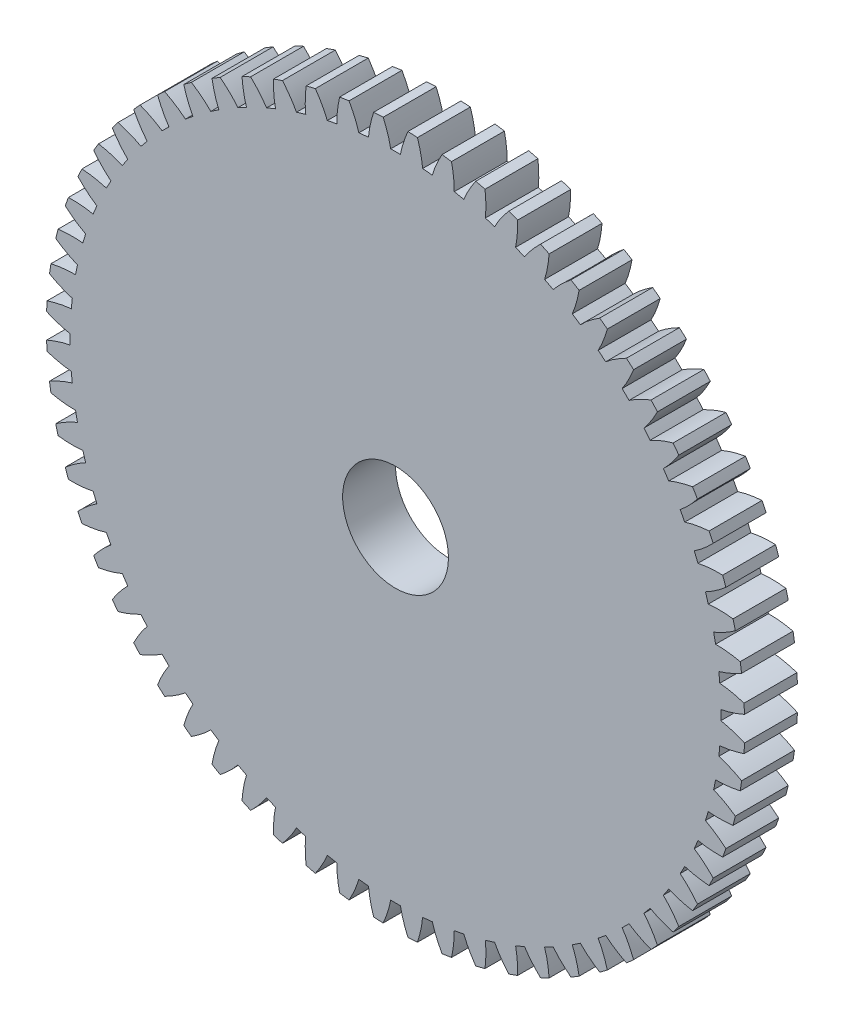
SolidWorks part; units mm, degrees
ref_plane "前视基准面" through (0, 0, 0) normal (0, 0, 1) x (1, 0, 0)
ref_plane "上视基准面" through (0, 0, 0) normal (0, 1, 0) x (1, 0, 0)
ref_plane "右视基准面" through (0, 0, 0) normal (1, 0, 0) x (0, 0, -1)
other "Configuration Table"
sketch "草图1" plane through (0, 0, 0) normal (0, 0, 1) x (1, 0, 0)
  line L0 (0, 0) -> (6.4, 0) construction
  line L1 (0, 0) -> (6.3981, 0.1571) construction
  line L2 (0, 0) -> (6.0135, 0.0774)
  line L3 (6.3981, 0.1571) -> (6.3981, -0.1571) construction
  line L4 (0, 0) -> (6.0135, -0.0774)
  circle A0 centre (0, 0) radius 6.6
  circle A1 centre (0, 0) radius 6.4 construction
  circle A2 centre (0, 0) radius 6.15
  circle A3 centre (0, 0) radius 6.014 construction
  circle A4 centre (0, 0) radius 1
  spline S0 degree 4 poles (6.0135, 0.0774) (6.0364, 0.0777) (6.0821, 0.0805) (6.2092, 0.0994) (6.4457, 0.1641) (6.7919, 0.3115) (7.2318, 0.5835) (7.7411, 1.0106) (8.2566, 1.5947) (8.7248, 2.311) (9.1179, 3.145) (9.4047, 4.0207) (9.5908, 4.9228) (9.686, 5.8846) (9.6791, 7.0814) (9.4879, 8.498) (9.0278, 10.0946) (8.2487, 11.7677) (7.2377, 13.3106) (6.0282, 14.7025) (4.6513, 15.9284) (3.1363, 16.9779) (1.7135, 17.7363) (0.5462, 18.2255) (-0.3224, 18.5269) (-0.982, 18.7296) (-1.647, 18.9089) (-2.322, 19.0593) (-2.9983, 19.1806) (-3.571, 19.2628) (-4.02, 19.3168) (-4.4511, 19.3563) (-4.803, 19.3824) (-5.2049, 19.403) (-5.4653, 19.4122) (-5.886, 19.421) (-6.2134, 19.4187) (-6.6109, 19.4119) (-6.965, 19.3963) (-7.3463, 19.3746) (-7.7078, 19.3453) (-7.9912, 19.3185) (-8.1717, 19.298) (-8.2653, 19.2873) knots 0 0 0 0 0 0.002802 0.005604 0.015718 0.02996 0.048734 0.068727 0.096889 0.125051 0.153212 0.181374 0.209535 0.237696 0.271429 0.327752 0.384075 0.440398 0.496721 0.553044 0.609367 0.66569 0.722013 0.750174 0.764255 0.778336 0.806497 0.834659 0.84874 0.86282 0.876901 0.890982 0.900036 0.909091 0.920455 0.931818 0.943182 0.954545 0.965909 0.977273 0.988636 1 1 1 1 1 construction
  spline S1 degree 4 poles (6.0135, 0.0774) (6.0364, 0.0777) (6.0821, 0.0805) (6.2092, 0.0994) (6.4457, 0.1641) (6.7919, 0.3115) (7.2318, 0.5835) (7.7411, 1.0106) (8.2566, 1.5947) (8.7248, 2.311) (9.1179, 3.145) (9.4047, 4.0207) (9.5908, 4.9228) (9.686, 5.8846) (9.6791, 7.0814) (9.4879, 8.498) (9.0278, 10.0946) (8.2487, 11.7677) (7.2377, 13.3106) (6.0282, 14.7025) (4.6513, 15.9284) (3.1363, 16.9779) (1.7135, 17.7363) (0.5462, 18.2255) (-0.3224, 18.5269) (-0.982, 18.7296) (-1.647, 18.9089) (-2.322, 19.0593) (-2.9983, 19.1806) (-3.571, 19.2628) (-4.02, 19.3168) (-4.4511, 19.3563) (-4.803, 19.3824) (-5.1, 19.3976) (-5.2354, 19.4034) (-5.3025, 19.4059) knots 0 0 0 0 0 0.002802 0.005604 0.015718 0.02996 0.048734 0.068727 0.096889 0.125051 0.153212 0.181374 0.209535 0.237696 0.271429 0.327752 0.384075 0.440398 0.496721 0.553044 0.609367 0.66569 0.722013 0.750174 0.764255 0.778336 0.806497 0.834659 0.84874 0.86282 0.876901 0.890982 0.900036 0.909091 0.909091 0.909091 0.909091 0.909091
  spline S2 degree 4 poles (6.0135, -0.0774) (6.0364, -0.0777) (6.0821, -0.0805) (6.2092, -0.0994) (6.4457, -0.1641) (6.7919, -0.3115) (7.2318, -0.5835) (7.7411, -1.0106) (8.2566, -1.5947) (8.7248, -2.311) (9.1179, -3.145) (9.4047, -4.0207) (9.5908, -4.9228) (9.686, -5.8846) (9.6791, -7.0814) (9.4879, -8.498) (9.0278, -10.0946) (8.2487, -11.7677) (7.2377, -13.3106) (6.0282, -14.7025) (4.6513, -15.9284) (3.1363, -16.9779) (1.7135, -17.7363) (0.5462, -18.2255) (-0.3224, -18.5269) (-0.982, -18.7296) (-1.647, -18.9089) (-2.322, -19.0593) (-2.9983, -19.1806) (-3.571, -19.2628) (-4.02, -19.3168) (-4.4511, -19.3563) (-4.803, -19.3824) (-5.2049, -19.403) (-5.4653, -19.4122) (-5.886, -19.421) (-6.2134, -19.4187) (-6.6109, -19.4119) (-6.965, -19.3963) (-7.3463, -19.3746) (-7.7078, -19.3453) (-7.9912, -19.3185) (-8.1717, -19.298) (-8.2653, -19.2873) knots 0 0 0 0 0 0.002802 0.005604 0.015718 0.02996 0.048734 0.068727 0.096889 0.125051 0.153212 0.181374 0.209535 0.237696 0.271429 0.327752 0.384075 0.440398 0.496721 0.553044 0.609367 0.66569 0.722013 0.750174 0.764255 0.778336 0.806497 0.834659 0.84874 0.86282 0.876901 0.890982 0.900036 0.909091 0.920455 0.931818 0.943182 0.954545 0.965909 0.977273 0.988636 1 1 1 1 1 construction
  spline S3 degree 4 poles (6.0135, -0.0774) (6.0364, -0.0777) (6.0821, -0.0805) (6.2092, -0.0994) (6.4457, -0.1641) (6.7919, -0.3115) (7.2318, -0.5835) (7.7411, -1.0106) (8.2566, -1.5947) (8.7248, -2.311) (9.1179, -3.145) (9.4047, -4.0207) (9.5908, -4.9228) (9.686, -5.8846) (9.6791, -7.0814) (9.4879, -8.498) (9.0278, -10.0946) (8.2487, -11.7677) (7.2377, -13.3106) (6.0282, -14.7025) (4.6513, -15.9284) (3.1363, -16.9779) (1.7135, -17.7363) (0.5462, -18.2255) (-0.3224, -18.5269) (-0.982, -18.7296) (-1.647, -18.9089) (-2.322, -19.0593) (-2.9983, -19.1806) (-3.571, -19.2628) (-4.02, -19.3168) (-4.4511, -19.3563) (-4.803, -19.3824) (-5.1, -19.3976) (-5.2354, -19.4034) (-5.3025, -19.4059) knots 0 0 0 0 0 0.002802 0.005604 0.015718 0.02996 0.048734 0.068727 0.096889 0.125051 0.153212 0.181374 0.209535 0.237696 0.271429 0.327752 0.384075 0.440398 0.496721 0.553044 0.609367 0.66569 0.722013 0.750174 0.764255 0.778336 0.806497 0.834659 0.84874 0.86282 0.876901 0.890982 0.900036 0.909091 0.909091 0.909091 0.909091 0.909091
  point P15 (6.3981, 0)
  dimension "齿顶圆直径" = 13.2
  dimension "分度圆直径" = 12.8
  dimension "齿根圆直径" = 12.3
  dimension "基圆直径" = 12.0281
  dimension "内孔直径" = 2
  dimension "渐近线镜像线夹角" = 1.406
extrude "凸台-拉伸1" add sketch "草图1" along normal blind 1 contours A0 | A4
extrude "切除-拉伸1" cut sketch "草图1<3>" along normal through all contours A2 S3 A0 S1 region at (6.4092, 0, 0)
sketch "草图1<3>" plane through (0, 0, 0) normal (0, 0, 1) x (1, 0, 0) same geometry as "草图1"
pattern_circular "阵列(圆周)1" count 64 every 5.625 about axis through (0, 0, 1) along (0, 0, 1) of "切除-拉伸1"
equation "\"m\"= 0.2'模数"
equation "\"z\" = 64'齿数"
equation "\"a\"= 20度'压力角"
equation "\"d\"= \"m\" * \"z\"'分度圆直径"
equation "\"da\"= ( \"z\" + 2 ) * \"m\"'齿顶圆直径"
equation "\"df\"= ( \"z\" - 2.5 ) * \"m\"'齿根圆直径"
equation "\"s\"= 0.5 * PI * \"m\"'分度圆齿厚"
equation "\"r\"= 0.38 * \"m\"'齿根圆角"
equation "\"B\"= 0.3 * \"d\"'齿厚"
equation "\"db\"= \"m\" * \"z\" * cos ( \"a\" )'基圆直径"
equation "\"rb\"= \"db\" / 2'基圆半径"
equation "\"齿顶圆直径@草图1\"= \"da\""
equation "\"分度圆直径@草图1\"= \"d\""
equation "\"齿根圆直径@草图1\"= \"df\""
equation "\"基圆直径@草图1\"= \"db\""
equation "\"渐近线镜像线夹角@草图1\"= 360 / 4 / \"z\""
equation "\"h\"= 1'齿轮厚度"
equation "\"ir\"= 2'内孔直径"
equation "\"内孔直径@草图1\"= \"ir\""
equation "\"齿轮厚@凸台-拉伸1\"= \"h\""
equation "\"齿轮夹角@阵列(圆周)1\"= 360 / \"z\""
equation "\"齿数@阵列(圆周)1\"= \"z\""
